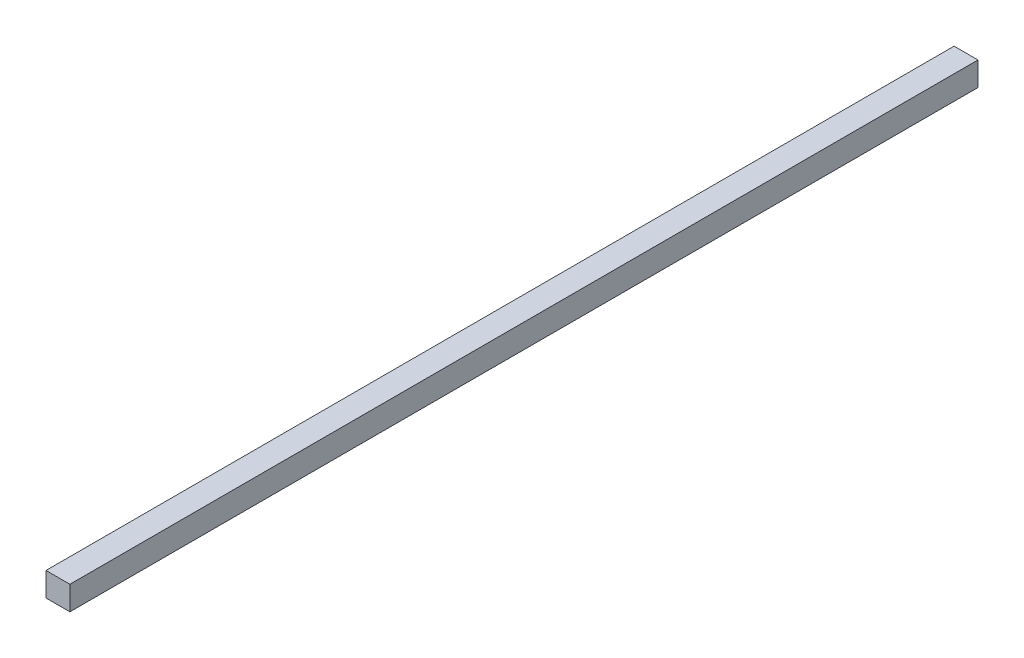
SolidWorks part; units mm, degrees
ref_plane "Front Plane" through (0, 0, 0) normal (0, 0, 1) x (1, 0, 0)
ref_plane "Top Plane" through (0, 0, 0) normal (0, 1, 0) x (1, 0, 0)
ref_plane "Right Plane" through (0, 0, 0) normal (1, 0, 0) x (0, 0, -1)
sketch "Sketch1" plane through (0, 0, 0) normal (1, 0, 0) x (0, 0, -1)
  line L1 (0, 0) -> (456, 0)
  line L2 (0, 0) -> (0, 12)
  line L3 (0, 12) -> (456, 12)
  line L4 (456, 0) -> (456, 12)
  dimension "D1" = 456
  dimension "D2" = 12
extrude "Boss-Extrude1" add sketch "Sketch1" along normal blind 12
